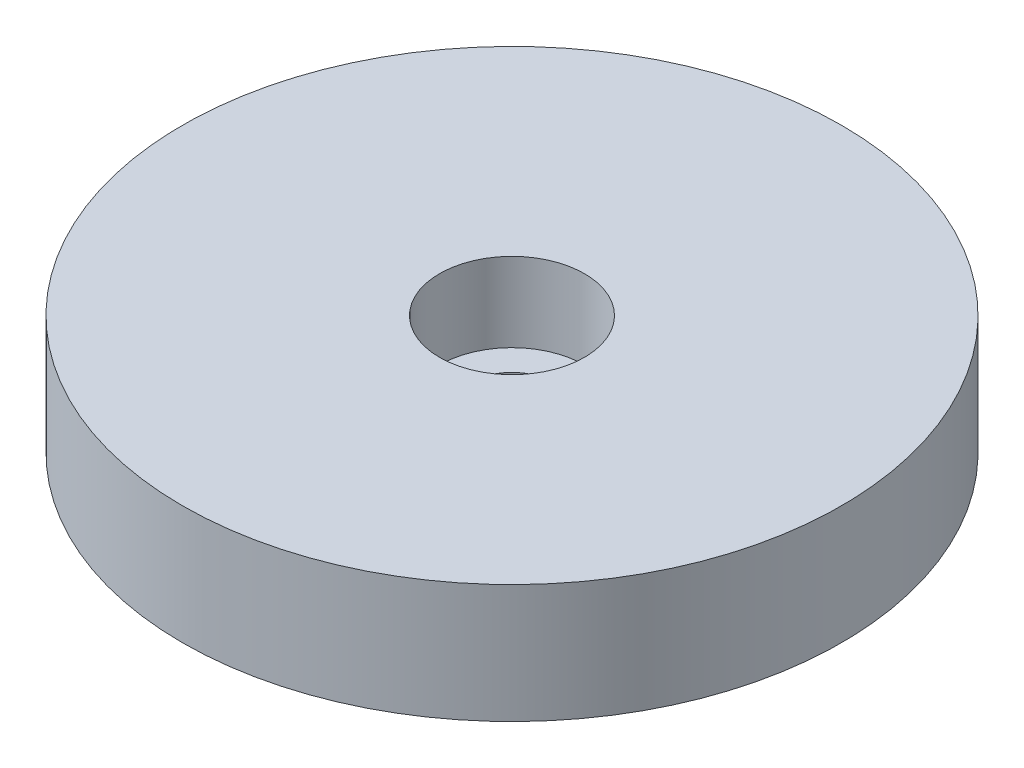
SolidWorks part; units mm, degrees
ref_plane "Alzado" through (0, 0, 0) normal (0, 0, 1) x (1, 0, 0)
ref_plane "Planta" through (0, 0, 0) normal (0, 1, 0) x (1, 0, 0)
ref_plane "Vista lateral" through (0, 0, 0) normal (1, 0, 0) x (0, 0, -1)
sketch "Croquis1" plane through (0, 0, 0) normal (0, 1, 0) x (1, 0, 0)
  circle A0 centre (0, 0) radius 25
  circle A1 centre (0, 0) radius 3.2
  dimension "D1" = 50
  dimension "D2" = 6.4
extrude "Saliente-Extruir1" add sketch "Croquis1" along normal blind 9
sketch "Croquis3" plane through (0, 9, 0) normal (0, 1, 0) x (1, 0, 0)
  circle A0 centre (0, 0) radius 5.5
  dimension "D1" = 11
extrude "Cortar-Extruir1" cut sketch "Croquis3" against normal blind 6
